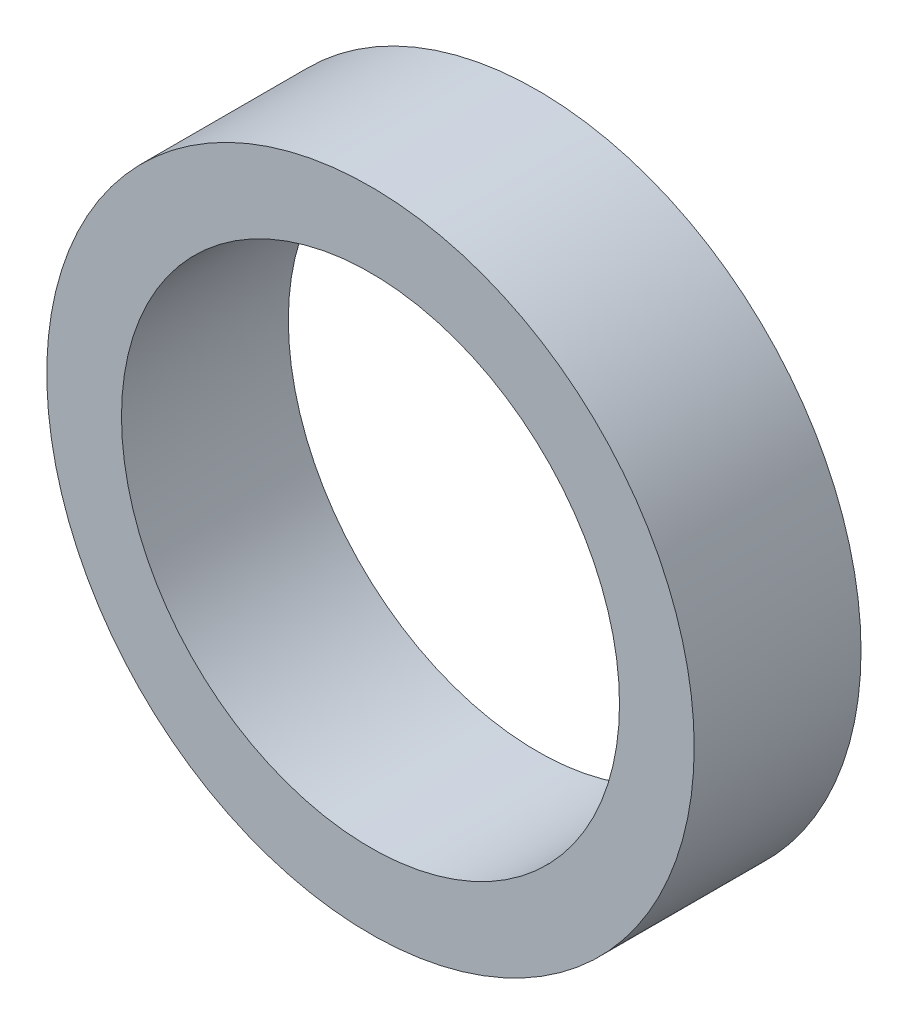
SolidWorks part; units mm, degrees
material "6061-T6 (SS)"
ref_plane "Front Plane" through (0, 0, 0) normal (0, 0, 1) x (1, 0, 0)
ref_plane "Top Plane" through (0, 0, 0) normal (0, 1, 0) x (1, 0, 0)
ref_plane "Right Plane" through (0, 0, 0) normal (1, 0, 0) x (0, 0, -1)
sketch "Sketch1" plane through (0, 0, 0) normal (0, 0, 1) x (1, 0, 0)
  circle A0 centre (0, 0) radius 5
  circle A1 centre (0, 0) radius 5
  circle A2 centre (0, 0) radius 6.5
  dimension "D1" = 13
extrude "Boss-Extrude1" add sketch "Sketch1" along normal up to surface (3.35 mm away)
